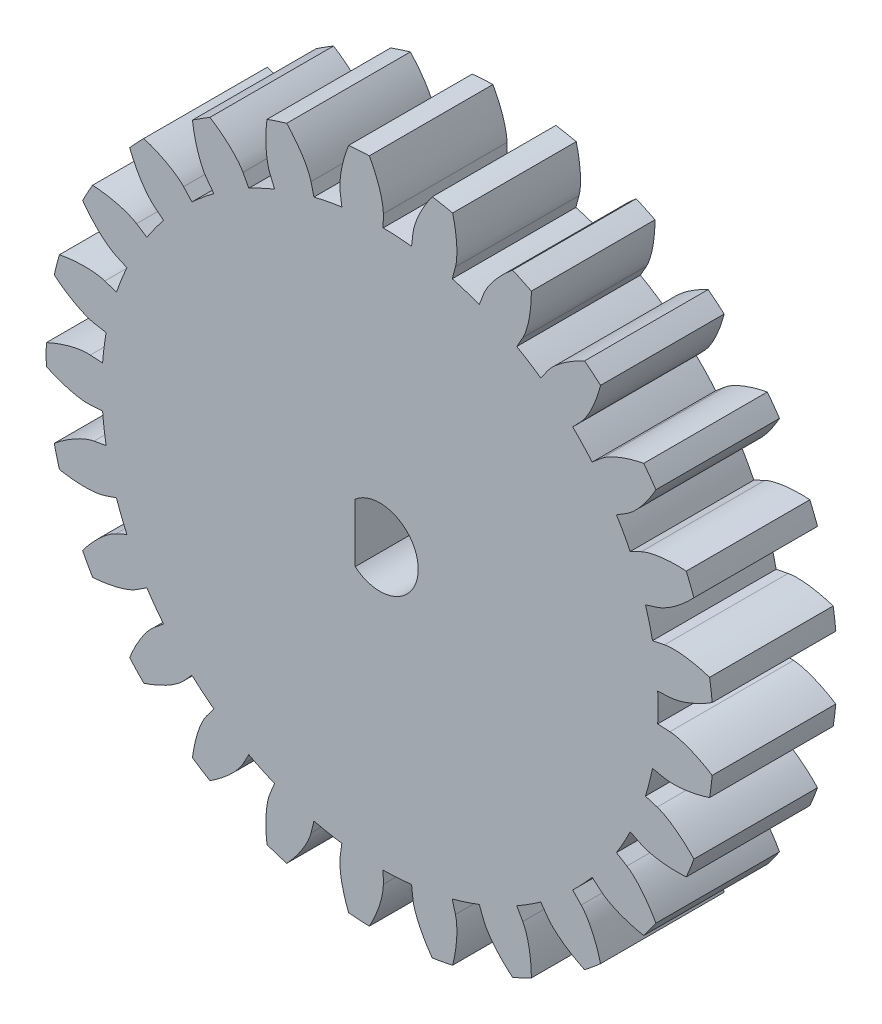
SolidWorks part; units mm, degrees
ref_plane "前视基准面" through (0, 0, 0) normal (0, 0, 1) x (1, 0, 0)
ref_plane "上视基准面" through (0, 0, 0) normal (0, 1, 0) x (1, 0, 0)
ref_plane "右视基准面" through (0, 0, 0) normal (1, 0, 0) x (0, 0, -1)
other "Configuration Table"
sketch "草图1" plane through (0, 0, 0) normal (0, 0, 1) x (1, 0, 0)
  line L0 (0, 0) -> (12.5, 0) construction
  line L1 (0, 0) -> (12.4753, 0.7849) construction
  line L2 (0, 0) -> (11.7308, 0.6006)
  line L3 (12.4753, 0.7849) -> (12.4753, -0.7849) construction
  line L4 (0, 0) -> (11.7308, -0.6006)
  circle A0 centre (0, 0) radius 13.5
  circle A1 centre (0, 0) radius 12.5 construction
  circle A2 centre (0, 0) radius 11.25
  circle A3 centre (0, 0) radius 11.7462 construction
  circle A4 centre (0, 0) radius 1.5
  spline S0 degree 4 poles (11.7308, 0.6006) (11.7755, 0.6029) (11.8643, 0.6116) (12.0316, 0.6433) (12.2735, 0.7093) (12.6814, 0.8559) (13.2995, 1.1611) (14.0704, 1.6798) (15.0324, 2.5516) (15.9945, 3.7303) (16.8544, 5.1636) (17.5588, 6.8208) (18.0528, 8.5514) (18.3481, 10.3262) (18.4616, 12.2104) (18.3582, 14.5457) (17.8786, 17.2961) (16.8605, 20.3774) (15.2143, 23.5842) (13.1252, 26.5195) (10.6599, 29.1451) (8.228, 31.1479) (5.9832, 32.6431) (4.0225, 33.738) (2.406, 34.5224) (0.7486, 35.2146) (-0.9455, 35.8144) (-3.0984, 36.4487) (-5.2958, 36.9294) (-7.181, 37.2087) (-8.7509, 37.3533) (-9.638, 37.4137) (-10.2546, 37.4438) (-10.8267, 37.4645) (-11.6179, 37.4744) (-12.1248, 37.4729) (-12.9482, 37.4584) (-13.5859, 37.4293) (-14.3618, 37.3861) (-15.0512, 37.329) (-15.7942, 37.2581) (-16.4973, 37.1736) (-17.0484, 37.1) (-17.3991, 37.0465) (-17.5812, 37.0186) knots 0 0 0 0 0 0.002802 0.005604 0.010661 0.015718 0.02996 0.048734 0.068727 0.096889 0.125051 0.153212 0.181374 0.209535 0.237696 0.271429 0.327752 0.384075 0.440398 0.496721 0.553044 0.609367 0.637529 0.66569 0.693852 0.722013 0.750174 0.778336 0.834659 0.86282 0.869861 0.876901 0.890982 0.900036 0.909091 0.920455 0.931818 0.943182 0.954545 0.965909 0.977273 0.988636 1 1 1 1 1 construction
  spline S1 degree 4 poles (11.7308, 0.6006) (11.7755, 0.6029) (11.8643, 0.6116) (12.0316, 0.6433) (12.2735, 0.7093) (12.6814, 0.8559) (13.2995, 1.1611) (14.0704, 1.6798) (15.0324, 2.5516) (15.9945, 3.7303) (16.8544, 5.1636) (17.5588, 6.8208) (18.0528, 8.5514) (18.3481, 10.3262) (18.4616, 12.2104) (18.3582, 14.5457) (17.8786, 17.2961) (16.8605, 20.3774) (15.2143, 23.5842) (13.1252, 26.5195) (10.6599, 29.1451) (8.228, 31.1479) (5.9832, 32.6431) (4.0225, 33.738) (2.406, 34.5224) (0.7486, 35.2146) (-0.9455, 35.8144) (-3.0984, 36.4487) (-5.2958, 36.9294) (-7.181, 37.2087) (-8.7509, 37.3533) (-9.638, 37.4137) (-10.2546, 37.4438) (-10.8267, 37.4645) (-11.4114, 37.4718) (-11.6764, 37.473) (-11.8076, 37.4728) knots 0 0 0 0 0 0.002802 0.005604 0.010661 0.015718 0.02996 0.048734 0.068727 0.096889 0.125051 0.153212 0.181374 0.209535 0.237696 0.271429 0.327752 0.384075 0.440398 0.496721 0.553044 0.609367 0.637529 0.66569 0.693852 0.722013 0.750174 0.778336 0.834659 0.86282 0.869861 0.876901 0.890982 0.900036 0.909091 0.909091 0.909091 0.909091 0.909091
  spline S2 degree 4 poles (11.7308, -0.6006) (11.7755, -0.6029) (11.8643, -0.6116) (12.0316, -0.6433) (12.2735, -0.7093) (12.6814, -0.8559) (13.2995, -1.1611) (14.0704, -1.6798) (15.0324, -2.5516) (15.9945, -3.7303) (16.8544, -5.1636) (17.5588, -6.8208) (18.0528, -8.5514) (18.3481, -10.3262) (18.4616, -12.2104) (18.3582, -14.5457) (17.8786, -17.2961) (16.8605, -20.3774) (15.2143, -23.5842) (13.1252, -26.5195) (10.6599, -29.1451) (8.228, -31.1479) (5.9832, -32.6431) (4.0225, -33.738) (2.406, -34.5224) (0.7486, -35.2146) (-0.9455, -35.8144) (-3.0984, -36.4487) (-5.2958, -36.9294) (-7.181, -37.2087) (-8.7509, -37.3533) (-9.638, -37.4137) (-10.2546, -37.4438) (-10.8267, -37.4645) (-11.6179, -37.4744) (-12.1248, -37.4729) (-12.9482, -37.4584) (-13.5859, -37.4293) (-14.3618, -37.3861) (-15.0512, -37.329) (-15.7942, -37.2581) (-16.4973, -37.1736) (-17.0484, -37.1) (-17.3991, -37.0465) (-17.5812, -37.0186) knots 0 0 0 0 0 0.002802 0.005604 0.010661 0.015718 0.02996 0.048734 0.068727 0.096889 0.125051 0.153212 0.181374 0.209535 0.237696 0.271429 0.327752 0.384075 0.440398 0.496721 0.553044 0.609367 0.637529 0.66569 0.693852 0.722013 0.750174 0.778336 0.834659 0.86282 0.869861 0.876901 0.890982 0.900036 0.909091 0.920455 0.931818 0.943182 0.954545 0.965909 0.977273 0.988636 1 1 1 1 1 construction
  spline S3 degree 4 poles (11.7308, -0.6006) (11.7755, -0.6029) (11.8643, -0.6116) (12.0316, -0.6433) (12.2735, -0.7093) (12.6814, -0.8559) (13.2995, -1.1611) (14.0704, -1.6798) (15.0324, -2.5516) (15.9945, -3.7303) (16.8544, -5.1636) (17.5588, -6.8208) (18.0528, -8.5514) (18.3481, -10.3262) (18.4616, -12.2104) (18.3582, -14.5457) (17.8786, -17.2961) (16.8605, -20.3774) (15.2143, -23.5842) (13.1252, -26.5195) (10.6599, -29.1451) (8.228, -31.1479) (5.9832, -32.6431) (4.0225, -33.738) (2.406, -34.5224) (0.7486, -35.2146) (-0.9455, -35.8144) (-3.0984, -36.4487) (-5.2958, -36.9294) (-7.181, -37.2087) (-8.7509, -37.3533) (-9.638, -37.4137) (-10.2546, -37.4438) (-10.8267, -37.4645) (-11.4114, -37.4718) (-11.6764, -37.473) (-11.8076, -37.4728) knots 0 0 0 0 0 0.002802 0.005604 0.010661 0.015718 0.02996 0.048734 0.068727 0.096889 0.125051 0.153212 0.181374 0.209535 0.237696 0.271429 0.327752 0.384075 0.440398 0.496721 0.553044 0.609367 0.637529 0.66569 0.693852 0.722013 0.750174 0.778336 0.834659 0.86282 0.869861 0.876901 0.890982 0.900036 0.909091 0.909091 0.909091 0.909091 0.909091
  point P15 (12.4753, 0)
  dimension "齿顶圆直径" = 27
  dimension "分度圆直径" = 25
  dimension "齿根圆直径" = 22.5
  dimension "基圆直径" = 23.4923
  dimension "内孔直径" = 3
  dimension "渐近线镜像线夹角" = 3.6
extrude "凸台-拉伸1" add sketch "草图1" along normal blind 5 contours A0 | A4
extrude "切除-拉伸1" cut sketch "草图1<3>" along normal through all contours A2 S3 A0 S1 region at (12.5298, 0, 0)
sketch "草图1<3>" plane through (0, 0, 0) normal (0, 0, 1) x (1, 0, 0) same geometry as "草图1"
pattern_circular "阵列(圆周)1" count 25 every 14.4 about axis through (0, 0, 5) along (0, 0, 1) of "切除-拉伸1"
sketch "草图2" plane through (0, 0, 0) normal (0, 0, -1) x (-1, 0, 0)
  line L0 (1, 1.1843) -> (1, -1.1843)
  circle A0 centre (0, 0) radius 1.55
  dimension "D1" = 3.1
  dimension "D2" = 1
extrude "凸台-拉伸2" add sketch "草图2" against normal through all contours A0
extrude "切除-拉伸2" cut sketch "草图2<3>" against normal through all contours L0 A0 region at (0.1667, 0, 0)
sketch "草图2<3>" plane through (0, 0, 0) normal (0, 0, -1) x (-1, 0, 0) same geometry as "草图2"
equation "\"m\"= 1'模数"
equation "\"z\"= 25'齿数"
equation "\"a\"= 20度'压力角"
equation "\"d\"= \"m\" * \"z\"'分度圆直径"
equation "\"da\"= ( \"z\" + 2 ) * \"m\"'齿顶圆直径"
equation "\"df\"= ( \"z\" - 2.5 ) * \"m\"'齿根圆直径"
equation "\"s\"= 0.5 * PI * \"m\"'分度圆齿厚"
equation "\"r\"= 0.38 * \"m\"'齿根圆角"
equation "\"B\"= 0.3 * \"d\"'齿厚"
equation "\"db\"= \"m\" * \"z\" * cos ( \"a\" )'基圆直径"
equation "\"rb\"= \"db\" / 2'基圆半径"
equation "\"齿顶圆直径@草图1\"= \"da\""
equation "\"分度圆直径@草图1\"= \"d\""
equation "\"齿根圆直径@草图1\"= \"df\""
equation "\"基圆直径@草图1\"= \"db\""
equation "\"渐近线镜像线夹角@草图1\"= 360 / 4 / \"z\""
equation "\"h\"= 5'齿轮厚度"
equation "\"ir\"= 3'内孔直径"
equation "\"内孔直径@草图1\"= \"ir\""
equation "\"齿轮厚@凸台-拉伸1\"= \"h\""
equation "\"齿轮夹角@阵列(圆周)1\"= 360 / \"z\""
equation "\"齿数@阵列(圆周)1\"= \"z\""
